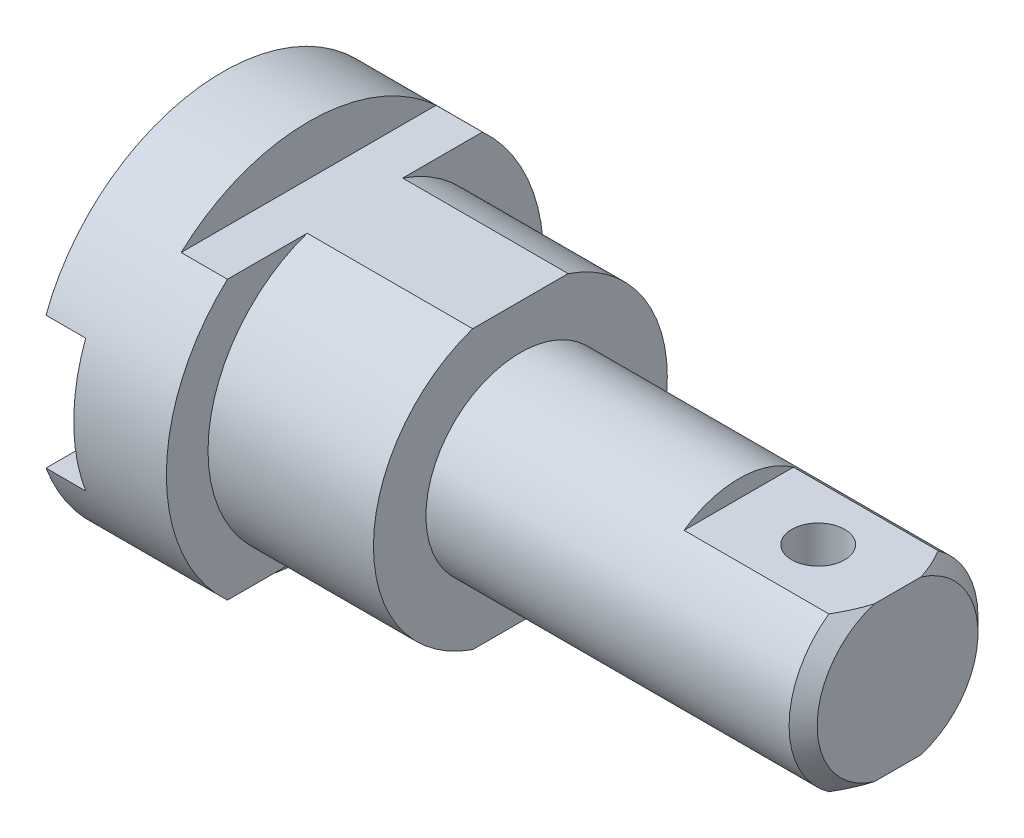
SolidWorks part; units mm, degrees
ref_plane "Front Plane" through (0, 0, 0) normal (0, 0, 1) x (1, 0, 0)
ref_plane "Top Plane" through (0, 0, 0) normal (0, 1, 0) x (1, 0, 0)
ref_plane "Right Plane" through (0, 0, 0) normal (1, 0, 0) x (0, 0, -1)
sketch "Sketch1" plane through (0, 0, 0) normal (0, 0, 1) x (1, 0, 0)
  line L0 (0, 0) -> (20, 0)
  line L1 (0, 0) -> (0, 57)
  line L2 (20, 0) -> (20, 57)
  line L3 (0, 57) -> (20, 57)
  line L4 (0, 18.5) -> (20, 0) construction
  line L9 (0, 38.5) -> (20, 57) construction
  line L10 (20, 0) -> (45, 6.295) construction
  line L11 (20, 50.705) -> (45, 50.705)
  line L12 (20, 50.705) -> (20, 6.295)
  line L13 (20, 6.295) -> (45, 6.295)
  line L14 (45, 50.705) -> (45, 6.295)
  line L15 (45, 50.705) -> (20, 57) construction
  line L16 (45, 6.295) -> (102, 14.225) construction
  line L17 (45, 42.775) -> (102, 42.775)
  line L18 (45, 42.775) -> (45, 14.225)
  line L19 (45, 14.225) -> (99.8787, 14.225)
  line L20 (102, 42.775) -> (102, 16.3463)
  line L21 (102, 42.775) -> (45, 50.705) construction
  line L22 (0, 28.5) -> (102, 28.5)
  line L23 (99.8787, 14.225) -> (102, 16.3463)
  line L24 (0, 38.5) -> (6, 38.5)
  line L25 (0, 38.5) -> (0, 18.5)
  line L26 (0, 18.5) -> (6, 18.5)
  line L27 (6, 38.5) -> (6, 18.5)
  dimension "D1" = 20
  dimension "D2" = 20
  dimension "D3" = 57
  dimension "D4" = 25
  dimension "D5" = 44.41
  dimension "D6" = 102
  dimension "D7" = 28.55
  dimension "D8" = 6
  dimension "D9" = 3
  dimension "D10" = 45
revolve "Revolve2" add sketch "Sketch1" angle 360 about L22 region at (10.8235, 13.1618, 0) region at (3, 23.5, 0) region at (32.5, 17.3975, 0) region at (73.4229, 21.3803, 0)
extrude "Cut-Extrude1" cut sketch "Sketch1<6>" against normal through all both and the other way through all contours L22 L1 L26 L2 | L25 L22 L12 L24 region at (3, 23.5, 0) region at (3, 33.5, 0)
sketch "Sketch1<6>" plane through (0, 0, 0) normal (0, 0, 1) x (1, 0, 0) same geometry as "Sketch1"
sketch "Sketch2" plane through (102, 0, 0) normal (1, 0, 0) x (0, 0, -1)
  line L0 (-8.2635, 40.14) -> (8.2635, 40.14)
  line L1 (0, 28.5) -> (14.275, 28.5) construction
  line L2 (-8.2635, 16.86) -> (8.2635, 16.86)
  circle A0 centre (0, 28.5) radius 14.275
  circle M5 centre (0, 28.5) radius 12.1537
  dimension "D2" = 28.55
  dimension "D1" = 23.28
extrude "Cut-Extrude2" cut sketch "Sketch2" against normal blind 24 contours L0 M5 | L0 A0 M5 | L2 A0 M5 | L2 M5 region at (102, 41.2785, 0) region at (102, 40.3458, 0) region at (102, 15.7215, 0) region at (102, 16.6542, 0)
sketch "Sketch3" plane through (0, 40.14, 0) normal (0, 1, 0) x (1, 0, 0)
  line L0 (102, 3.496) -> (102, -3.496) construction
  circle A0 centre (90, 0) radius 4
  dimension "D1" = 8
  dimension "D2" = 12
extrude "Cut-Extrude3" cut sketch "Sketch3" against normal through all
sketch "Sketch4" plane through (20, 0, 0) normal (1, 0, 0) x (0, 0, -1)
  line L0 (-19.2678, 49.5) -> (19.2678, 49.5)
  line L1 (0, 28.5) -> (28.5, 28.5) construction
  line L2 (-19.2678, 7.5) -> (19.2678, 7.5)
  circle A0 centre (0, 28.5) radius 28.5
  circle M5 centre (0, 28.5) radius 22.205
  circle M6 centre (0, 28.5) radius 28.5
  dimension "D1" = 42
extrude "Cut-Extrude4" cut sketch "Sketch4" against normal blind 7 and the other way blind 25 contours L0 M6 M5 | L0 M5 | L2 M5 | L2 M6 M5 region at (20, 52.696, 0) region at (20, 49.9831, 0) region at (20, 4.304, 0) region at (20, 7.0169, 0)
